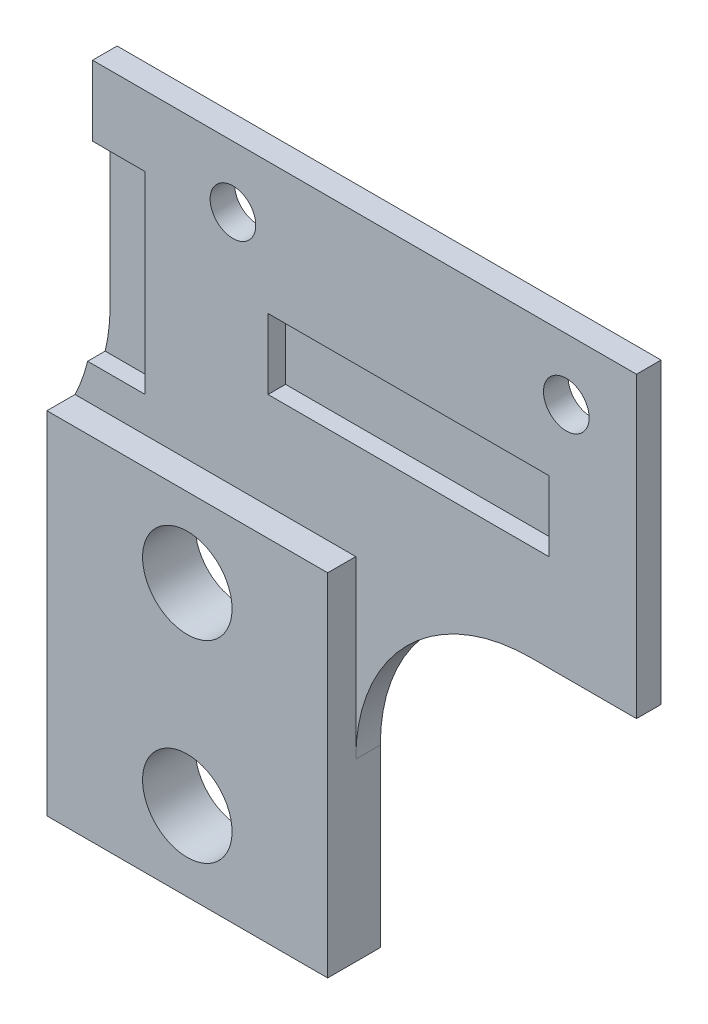
SolidWorks part; units mm, degrees
ref_plane "Front Plane" through (0, 0, 0) normal (0, 0, 1) x (1, 0, 0)
ref_plane "Top Plane" through (0, 0, 0) normal (0, 1, 0) x (1, 0, 0)
ref_plane "Right Plane" through (0, 0, 0) normal (1, 0, 0) x (0, 0, -1)
sketch "Sketch1" plane through (0, 0, 0) normal (0, 0, 1) x (1, 0, 0)
  line L1 (-20, -8.5) -> (20, -8.5)
  line L2 (-20, -8.5) -> (-20, 8.5)
  line L3 (-20, 8.5) -> (20, 8.5)
  line L4 (20, -8.5) -> (20, 8.5)
  line L5 (-20, -8.5) -> (20, 8.5) construction
  line L6 (-20, 8.5) -> (20, -8.5) construction
  point P0 (0, 0)
extrude "Boss-Extrude1" add sketch "Sketch1" along normal blind 1.4
sketch "Sketch3" plane through (0, 0, 0) normal (0, 0, 1) x (1, 0, 0)
  line L1 (20, -8.5) -> (20, 8.5) construction
  line L2 (20, 8.5) -> (20, 0.5) construction
  line L3 (20, 8.5) -> (-20, 8.5) construction
  line L4 (-20, 8.5) -> (-20, 4.5) construction
  line L5 (-1, 1) -> (15, 1)
  line L6 (-1, 1) -> (-1, -3)
  line L7 (-1, -3) -> (15, -3)
  line L8 (15, 1) -> (15, -3)
  line L10 (-20, 8.5) -> (-20, -8.5) construction
  line L11 (-20, 4.5) -> (-11, 4.5) construction
  line L13 (-11, 4.5) -> (-8, 4.5)
  line L14 (-11, 4.5) -> (-11, -6.5)
  line L15 (-11, -6.5) -> (-8, -6.5)
  line L16 (-8, 4.5) -> (-8, -6.5)
extrude "Cut-Extrude1" cut sketch "Sketch3" against normal blind 1 from surface starting at face at (0, 0, 1.4)
sketch "Sketch4" plane through (0, 0, 0) normal (0, 0, 1) x (1, 0, 0)
  line L0 (20, 8.5) -> (16, 8.5) construction
  line L1 (20, 8.5) -> (-20, 8.5) construction
  line L2 (16, 8.5) -> (16, 5) construction
  line L3 (16, 5) -> (-3, 5) construction
  circle A0 centre (16, 5) radius 1.3
  circle A1 centre (-3, 5) radius 1.3
extrude "Cut-Extrude2" cut sketch "Sketch4" along normal blind 11
sketch "Sketch7" plane through (0, 0, 0) normal (0, 0, 1) x (1, 0, 0)
  line L0 (-20, -8.5) -> (20, -8.5) construction
  line L1 (-20, 8.5) -> (-11, 8.5)
  line L2 (-20, 8.5) -> (-20, -8.5)
  line L3 (-20, -8.5) -> (-11, -8.5)
  line L4 (-11, 8.5) -> (-11, -8.5)
extrude "Cut-Extrude5" cut sketch "Sketch7" along normal blind 21
sketch "Sketch9" plane through (0, 0, 0) normal (0, 0, 1) x (1, 0, 0)
  line L0 (-3, 5) -> (16, 5) construction
  line L15 (-1.7, 5) -> (-1.7, -8.5) construction
  line L17 (-11, -8.5) -> (20, -8.5) construction
  line L19 (-12, -8.5) -> (-12, -28.5)
  line L20 (-1.7, -8.5) -> (-4, -8.5) construction
  line L22 (-4, -8.5) -> (-4, -13) construction
  line L26 (-4, -13) -> (-4, -24) construction
  line L27 (-4, -8.5) -> (-12, -8.5)
  line L28 (-4, -8.5) -> (4, -8.5)
  line L29 (4, -8.5) -> (4, -28.5)
  line L30 (4, -28.5) -> (-12, -28.5)
  circle A8 centre (-3, 5) radius 1.3 construction
  circle A9 centre (-4, -13) radius 2.55
  circle A10 centre (-4, -24) radius 2.55
extrude "Boss-Extrude3" add sketch "Sketch9" along normal blind 3
fillet "Fillet2" radius 10 2 edges at (-11, -8.5, 0.7) (4, -8.5, 0.7)
